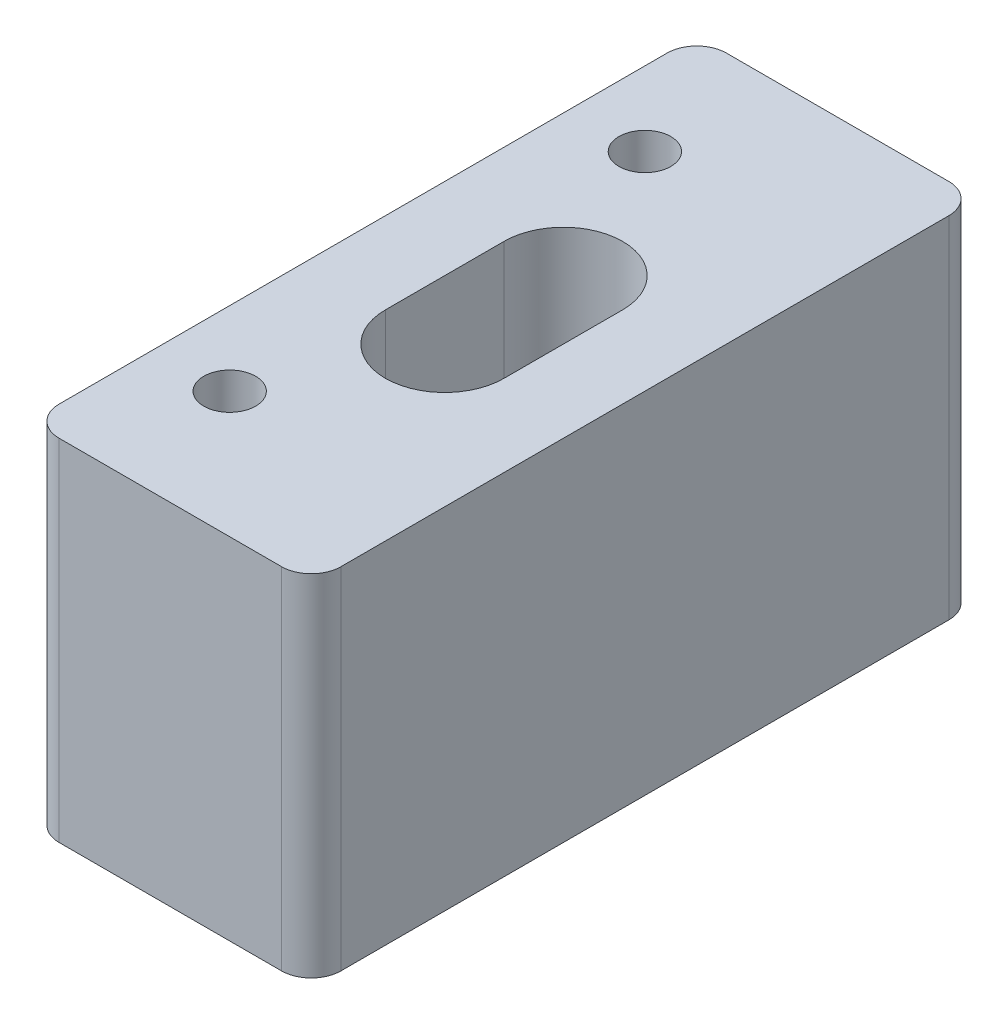
SolidWorks part; units mm, degrees
ref_plane "前视基准面" through (0, 0, 0) normal (0, 0, 1) x (1, 0, 0)
ref_plane "上视基准面" through (0, 0, 0) normal (0, 1, 0) x (1, 0, 0)
ref_plane "右视基准面" through (0, 0, 0) normal (1, 0, 0) x (0, 0, -1)
other "Configuration Table"
sketch "草图1" plane through (0, 0, 0) normal (0, 1, 0) x (1, 0, 0)
  line L0 (0, 14) -> (0, -14) construction
  line L2 (-5, 22.5) -> (14, 22.5)
  line L3 (-5, 22.5) -> (-5, -22.5)
  line L4 (-5, -22.5) -> (14, -22.5)
  line L5 (14, 22.5) -> (14, -22.5)
  circle A0 centre (0, -14) radius 1.75
  circle A1 centre (0, 14) radius 1.75
  point P9 (14, 0)
  dimension "D2" = 3.5
  dimension "D1" = 28
  dimension "D3" = 45
  dimension "D4" = 5
  dimension "D5" = 19
extrude "凸台-拉伸1" add sketch "草图1" along normal blind 2
fillet "圆角1" radius 2 4 edges at (-5, 1, -22.5) (14, 1, -22.5) (-5, 1, 22.5) (14, 1, 22.5)
sketch "草图3" plane through (0, 2, 0) normal (0, 1, 0) x (1, 0, 0)
  line L0 (4.5, 4) -> (4.5, -4) construction
  line L1 (8.5, 4) -> (8.5, -4)
  line L2 (0.5, 4) -> (0.5, -4)
  line L3 (-3, -22.5) -> (12, -22.5) construction
  arc A0 (8.5, 4) -> (0.5, 4) centre (4.5, 4) ccw
  arc A1 (0.5, -4) -> (8.5, -4) centre (4.5, -4) ccw
  point P2 (4.5, 0)
  point P10 (4.5, -22.5)
  dimension "D2" = 4
  dimension "D1" = 8
extrude "切除-拉伸1" cut sketch "草图3" against normal blind 2
sketch "草图4" plane through (0, 2, 0) normal (0, 1, 0) x (1, 0, 0)
  line L0 (8.5, -4) -> (8.5, 4) construction
  line L1 (0.5, 4) -> (0.5, -4) construction
  line L2 (8.5, -4) -> (8.5, 4)
  line L3 (0.5, 4) -> (0.5, -4)
  line L4 (12, 22.5) -> (-3, 22.5)
  line L5 (-5, 20.5) -> (-5, -20.5)
  line L6 (-3, -22.5) -> (12, -22.5)
  line L7 (14, -20.5) -> (14, 20.5)
  line L8 (12, 22.5) -> (-3, 22.5)
  line L9 (-5, 20.5) -> (-5, -20.5)
  line L10 (-3, -22.5) -> (12, -22.5)
  line L11 (14, -20.5) -> (14, 20.5)
  circle A0 centre (0, 14) radius 1.75 construction
  circle A1 centre (0, -14) radius 1.75 construction
  arc A2 (0.5, -4) -> (8.5, -4) centre (4.5, -4) ccw construction
  arc A3 (8.5, 4) -> (0.5, 4) centre (4.5, 4) ccw construction
  arc A4 (-3, 22.5) -> (-5, 20.5) centre (-3, 20.5) ccw
  arc A5 (-5, -20.5) -> (-3, -22.5) centre (-3, -20.5) ccw
  arc A6 (12, -22.5) -> (14, -20.5) centre (12, -20.5) ccw
  arc A7 (14, 20.5) -> (12, 22.5) centre (12, 20.5) ccw
  arc A8 (-3, 22.5) -> (-5, 20.5) centre (-3, 20.5) ccw
  arc A9 (-5, -20.5) -> (-3, -22.5) centre (-3, -20.5) ccw
  arc A10 (12, -22.5) -> (14, -20.5) centre (12, -20.5) ccw
  arc A11 (14, 20.5) -> (12, 22.5) centre (12, 20.5) ccw
  circle A12 centre (0, 14) radius 1.75
  circle A13 centre (0, -14) radius 1.75
  arc A14 (0.5, -4) -> (8.5, -4) centre (4.5, -4) ccw
  arc A15 (8.5, 4) -> (0.5, 4) centre (4.5, 4) ccw
  dimension "D1" = 0
extrude "凸台-拉伸2" add sketch "草图4" along normal up to surface (21.6127 mm away)
